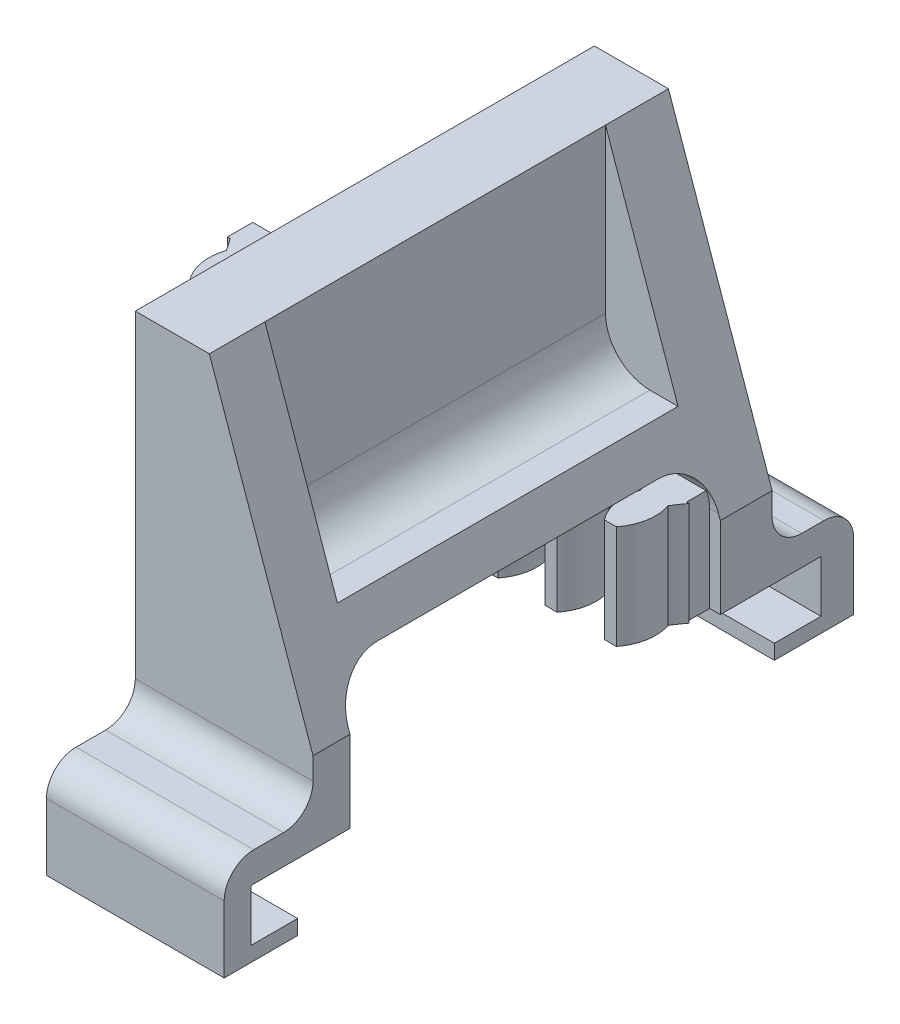
SolidWorks part; units mm, degrees
ref_plane "Front Plane" through (0, 0, 0) normal (0, 0, 1) x (1, 0, 0)
ref_plane "Top Plane" through (0, 0, 0) normal (0, 1, 0) x (1, 0, 0)
ref_plane "Right Plane" through (0, 0, 0) normal (1, 0, 0) x (0, 0, -1)
sketch "Sketch1" plane through (0, 0, 0) normal (0, 0, 1) x (1, 0, 0)
  line L0 (0, 0) -> (0, -30)
  line L1 (0, -30) -> (12, -30)
  line L2 (12, -30) -> (12, -20)
  line L3 (12, -20) -> (5, 0)
  line L4 (5, 0) -> (0, 0)
  dimension "D1" = 30
  dimension "D2" = 12
  dimension "D3" = 10
  dimension "D4" = 5
extrude "Boss-Extrude1" add sketch "Sketch1" against normal blind 31
sketch "Sketch4" plane through (0, 0, 0) normal (-1, 0, 0) x (0, 0, 1)
  line L0 (-31, 0) -> (-31, -30) construction
  line L1 (-27.5, -16.6434) -> (-2.5, -16.6434)
  line L2 (-27.5, -16.6434) -> (-27.5, -31.6434)
  line L3 (-27.5, -31.6434) -> (-2.5, -31.6434)
  line L4 (-2.5, -16.6434) -> (-2.5, -31.6434)
  point P4 (-27.5, -24.1434)
  dimension "D1" = 25
  dimension "D2" = 15
  dimension "D3" = 3.5
extrude "Cut-Extrude2" cut sketch "Sketch4" against normal blind 25 contours L2 L1 L4 L3
ref_plane "Plane1" through (0, 0, -15.25) normal (0, 0, 1) x (1, 0, 0)
sketch "Sketch6" plane through (0, 0, -15.25) normal (0, 0, 1) x (1, 0, 0)
  line L0 (5, 0) -> (5, -14)
  line L1 (5, -14) -> (9.9, -14)
  line L2 (12, -20) -> (5, 0) construction
  line L3 (9.9, -14) -> (5, 0)
  dimension "D1" = 14
extrude "Cut-Extrude4" cut sketch "Sketch6" against normal mid plane 23
ref_plane "Plane3" through (0, -25.5, 0) normal (0, 1, 0) x (1, 0, 0)
sketch "Sketch7" plane through (0, -25.5, 0) normal (0, 1, 0) x (1, 0, 0)
  line L0 (11.2768, 27.65) -> (-19.7232, 27.65)
  line L62 (-16.5, 15.25) -> (16.5, 15.25) construction
  line L162 (11.2768, 27.65) -> (11.2768, 25.95)
  line L172 (-19.7232, 25.95) -> (-19.7232, 27.65)
  line L243 (11.2768, 25.95) -> (-19.7232, 25.95)
  dimension "D2" = 31
  dimension "D3" = 1.7
  dimension "D7" = 12.4
extrude "Boss-Extrude3" add sketch "Sketch7" along normal blind 7
sketch "Sketch10" plane through (0, -25.5, 0) normal (0, 1, 0) x (1, 0, 0)
  line L1 (9.9522, 22.1269) -> (9.9522, 23.4692) construction
  line L2 (10.3536, 22.1269) -> (9.5507, 22.1269)
  line L4 (-19.7232, 25.95) -> (11.2768, 25.95) construction
  line L5 (8.4522, 25.95) -> (11.4522, 25.95)
  arc A0 (10.3536, 22.1269) -> (10.8746, 25.1093) centre (7.8655, 24.0983) ccw
  arc A1 (10.8746, 25.1093) -> (11.4522, 25.95) centre (19.0749, 20.0948) cw
  arc A2 (9.0297, 25.1093) -> (8.4522, 25.95) centre (0.8294, 20.0948) ccw
  arc A3 (9.5507, 22.1269) -> (9.0297, 25.1093) centre (12.0388, 24.0983) cw
  point P7 (9.5046, 21.9205)
  point P15 (9.5507, 22.1269)
  dimension "D1" = 3
extrude "Boss-Extrude4" add sketch "Sketch10" along normal blind 7
pattern_linear "LPattern1" count 8 spacing 4 along (-1, 0, 0) of "Boss-Extrude4"
sketch "Sketch11" plane through (0, 0, -31) normal (0, 0, -1) x (-1, 0, 0)
  line L0 (-12, -30) -> (-12, -20) construction
  line L1 (-12, -23.5) -> (0, -23.5)
  line L2 (-12, -23.5) -> (-12, -30)
  line L3 (-12, -30) -> (0, -30)
  line L4 (0, -23.5) -> (0, -30)
  dimension "D1" = 6.5
extrude "Boss-Extrude5" add sketch "Sketch11" along normal blind 5.5
fillet "Fillet5" radius 3 3 edges at (5, -14, -15.25) (5.4126, -16.6434, -2.5) (5.4126, -16.6434, -27.5)
sketch "Sketch12" plane through (0, 0, 0) normal (0, 0, 1) x (1, 0, 0)
  line L0 (12, -30) -> (12, -20) construction
  line L1 (0, -30) -> (12, -30)
  line L2 (0, -30) -> (0, -23.5)
  line L3 (0, -23.5) -> (12, -23.5)
  line L4 (12, -30) -> (12, -23.5)
  dimension "D1" = 6.5
extrude "Boss-Extrude6" add sketch "Sketch12" along normal blind 6
sketch "Sketch13" plane through (0, 0, 0) normal (-1, 0, 0) x (0, 0, 1)
  line L0 (-34.3, -25.5) -> (-27.5, -25.5)
  line L1 (-27.5, -25.5) -> (-27.5, -32.0691)
  line L2 (-27.5, -32.0691) -> (-31.15, -32.0691)
  line L3 (-31.15, -32.0691) -> (-31.15, -29)
  line L4 (-31.15, -29) -> (-34.3, -29)
  line L5 (-34.3, -29) -> (-34.3, -25.5)
  line L6 (-15.0561, -22.9316) -> (-15.0561, -37.9805) construction
  line L7 (-2.5, -30) -> (6, -30) construction
  line L9 (-27.5, -25.5) -> (-27.5, -30) construction
  line L12 (1.0378, -29) -> (4.1878, -29)
  line L13 (1.0378, -32.0691) -> (1.0378, -29)
  line L14 (-2.6122, -32.0691) -> (1.0378, -32.0691)
  line L15 (-2.6122, -25.5) -> (-2.6122, -32.0691)
  line L16 (4.1878, -25.5) -> (-2.6122, -25.5)
  line L17 (4.1878, -29) -> (4.1878, -25.5)
  dimension "D1" = 6.8
  dimension "D2" = 0
  dimension "D3" = 3.65
  dimension "D4" = 3.5
  dimension "D5" = 4.5
extrude "Cut-Extrude5" cut sketch "Sketch13" against normal up to surface (12 mm away) up to face at (12, -24.5, 1.1667)
fillet "Fillet6" radius 2 4 edges at (6, -23.5, -36.5) (6, -23.5, -31) (6, -23.5, 6) (6, -23.5, 0)
